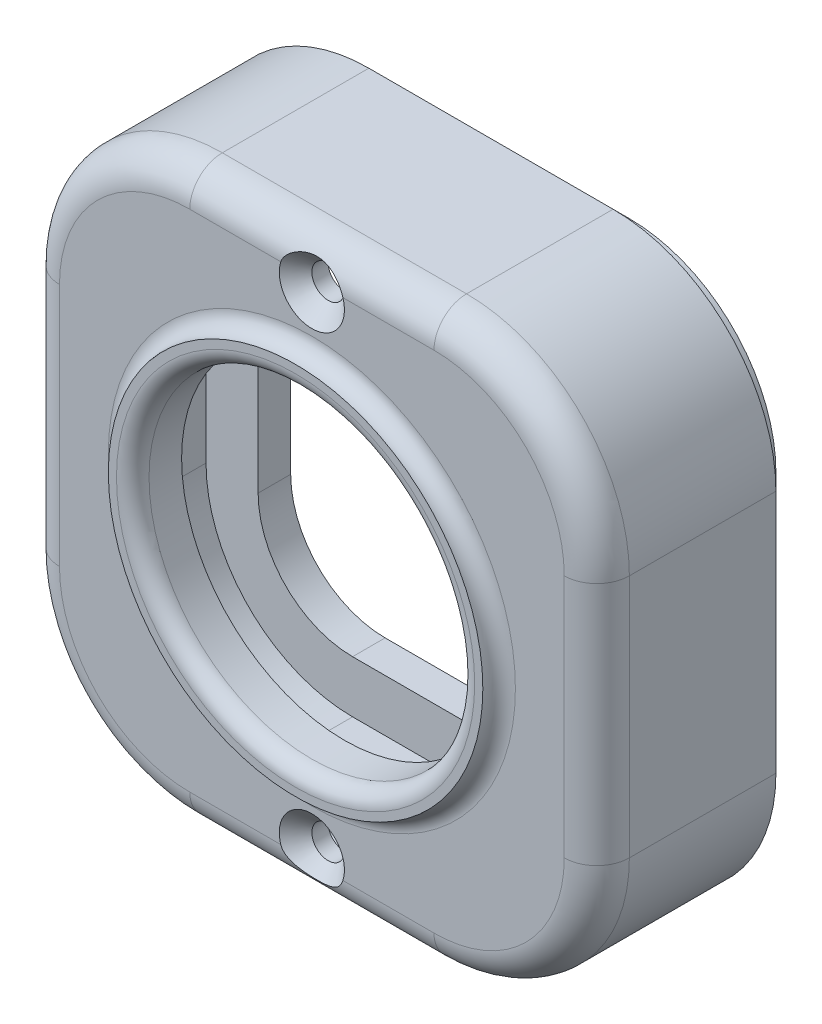
SolidWorks part; units mm, degrees
ref_plane "Front Plane" through (0, 0, 0) normal (0, 0, 1) x (1, 0, 0)
ref_plane "Top Plane" through (0, 0, 0) normal (0, 1, 0) x (1, 0, 0)
ref_plane "Right Plane" through (0, 0, 0) normal (1, 0, 0) x (0, 0, -1)
sketch "Sketch2" plane through (0, 0, 0) normal (0, 0, 1) x (1, 0, 0)
  line L0 (0, -22.225) -> (0, 22.225) construction
  line L1 (-9.525, -22.225) -> (9.525, -22.225)
  line L2 (-22.225, -9.525) -> (-22.225, 9.525)
  line L3 (-9.525, 22.225) -> (9.525, 22.225)
  line L4 (22.225, -9.525) -> (22.225, 9.525)
  line L5 (-22.225, 0) -> (22.225, 0) construction
  arc A0 (-9.525, -22.225) -> (-22.225, -9.525) centre (-9.525, -9.525) cw
  arc A1 (9.525, -22.225) -> (22.225, -9.525) centre (9.525, -9.525) ccw
  arc A2 (22.225, 9.525) -> (9.525, 22.225) centre (9.525, 9.525) ccw
  arc A3 (-22.225, 9.525) -> (-9.525, 22.225) centre (-9.525, 9.525) cw
  dimension "D3" = 12.7
  dimension "D4" = 22.225
  dimension "D5" = 22.225
  dimension "D1" = 19.05
  dimension "D2" = 19.05
extrude "Boss-Extrude1" add sketch "Sketch2" along normal blind 2.54
sketch "Sketch3" plane through (0, 0, 2.54) normal (0, 0, 1) x (1, 0, 0)
  circle A0 centre (0, 0) radius 14.605
  dimension "D1" = 29.21
extrude "Boss-Extrude2" add sketch "Sketch3" along normal blind 1.27
sketch "Sketch4" plane through (0, 0, 3.81) normal (0, 0, 1) x (1, 0, 0)
  circle A0 centre (0, 0) radius 12.7
  dimension "D1" = 25.4
extrude "Cut-Extrude1" cut sketch "Sketch4" against normal through all both and the other way through all
sketch "Sketch5" plane through (0, 0, 0) normal (0, 0, -1) x (-1, 0, 0)
  line L14 (-22.225, 9.525) -> (-22.225, -9.525)
  line L15 (-9.525, -22.225) -> (9.525, -22.225)
  line L16 (22.225, -9.525) -> (22.225, 9.525)
  line L17 (9.525, 22.225) -> (-9.525, 22.225)
  line L18 (-9.525, 20.955) -> (9.525, 20.955)
  line L19 (-20.955, 9.525) -> (-20.955, -9.525)
  line L20 (-9.525, -20.955) -> (9.525, -20.955)
  line L21 (20.955, -9.525) -> (20.955, 9.525)
  arc A0 (-9.525, 20.955) -> (-20.955, 9.525) centre (-9.525, 9.525) ccw
  arc A1 (-20.955, -9.525) -> (-9.525, -20.955) centre (-9.525, -9.525) ccw
  arc A10 (22.225, 9.525) -> (9.525, 22.225) centre (9.525, 9.525) ccw construction
  arc A11 (-9.525, 22.225) -> (-22.225, 9.525) centre (-9.525, 9.525) ccw
  arc A12 (-22.225, -9.525) -> (-9.525, -22.225) centre (-9.525, -9.525) ccw
  arc A13 (9.525, -22.225) -> (22.225, -9.525) centre (9.525, -9.525) ccw
  arc A14 (22.225, 9.525) -> (9.525, 22.225) centre (9.525, 9.525) ccw
  arc A19 (9.525, -20.955) -> (20.955, -9.525) centre (9.525, -9.525) ccw
  arc A20 (20.955, 9.525) -> (9.525, 20.955) centre (9.525, 9.525) ccw
  dimension "D1" = 1.27
  dimension "D2" = 1.27
  dimension "D3" = 1.27
  dimension "D4" = 1.27
extrude "Boss-Extrude3" add sketch "Sketch5" along normal blind 11.43
sketch "Sketch6" plane through (0, 0, -11.43) normal (0, 0, -1) x (-1, 0, 0)
  line L16 (-9.525, 20.955) -> (9.525, 20.955)
  line L17 (20.955, 9.525) -> (20.955, -9.525)
  line L18 (9.525, -20.955) -> (-9.525, -20.955)
  line L19 (-20.955, -9.525) -> (-20.955, 9.525)
  line L20 (-9.525, 16.891) -> (9.525, 16.891)
  line L21 (-16.891, 9.525) -> (-16.891, -9.525)
  line L22 (-9.525, -16.891) -> (9.525, -16.891)
  line L23 (16.891, -9.525) -> (16.891, 9.525)
  arc A19 (-9.525, 20.955) -> (-20.955, 9.525) centre (-9.525, 9.525) ccw
  arc A20 (-20.955, -9.525) -> (-9.525, -20.955) centre (-9.525, -9.525) ccw
  arc A21 (9.525, -20.955) -> (20.955, -9.525) centre (9.525, -9.525) ccw
  arc A22 (20.955, 9.525) -> (9.525, 20.955) centre (9.525, 9.525) ccw
  arc A23 (-9.525, 16.891) -> (-16.891, 9.525) centre (-9.525, 9.525) ccw
  arc A24 (-16.891, -9.525) -> (-9.525, -16.891) centre (-9.525, -9.525) ccw
  arc A25 (9.525, -16.891) -> (16.891, -9.525) centre (9.525, -9.525) ccw
  arc A26 (16.891, 9.525) -> (9.525, 16.891) centre (9.525, 9.525) ccw
  dimension "D1" = 4.064
  dimension "D5" = 7.366
  dimension "D2" = 4.064
  dimension "D3" = 4.064
  dimension "D4" = 4.064
extrude "Boss-Extrude5" add sketch "Sketch6" along normal blind 2.54 from offset 1.27 offset against normal yes
fillet "Fillet2" radius 1.27 2 edges at (14.605, 0, 2.54) (12.7, 0, 3.81)
sketch "Sketch7" plane through (0, 0, -12.7) normal (0, 0, -1) x (-1, 0, 0)
  line L0 (0, 20.955) -> (0, -20.955) construction
  line L1 (9.525, 20.955) -> (-9.525, 20.955) construction
  line L3 (-9.525, -20.955) -> (9.525, -20.955) construction
  circle A0 centre (0, 18.923) radius 1.27
  circle A1 centre (0, -18.923) radius 1.27
  dimension "D1" = 2.54
  dimension "D2" = 2.032
  dimension "D3" = 2.032
extrude "Cut-Extrude2" cut sketch "Sketch7" against normal through all both and the other way through all
chamfer "Chamfer1" distance 1.27 angle 45 2 edges at (-1.27, 18.923, 2.54) (-1.27, -18.923, 2.54)
fillet "Fillet3" radius 2.54 8 edges at (-18.5053, 18.5053, 2.54) (0, 22.225, 2.54) (18.5053, 18.5053, 2.54) (22.225, 0, 2.54) (18.5053, -18.5053, 2.54) (0, -22.225, 2.54) (-18.5053, -18.5053, 2.54) (-22.225, 0, 2.54)
